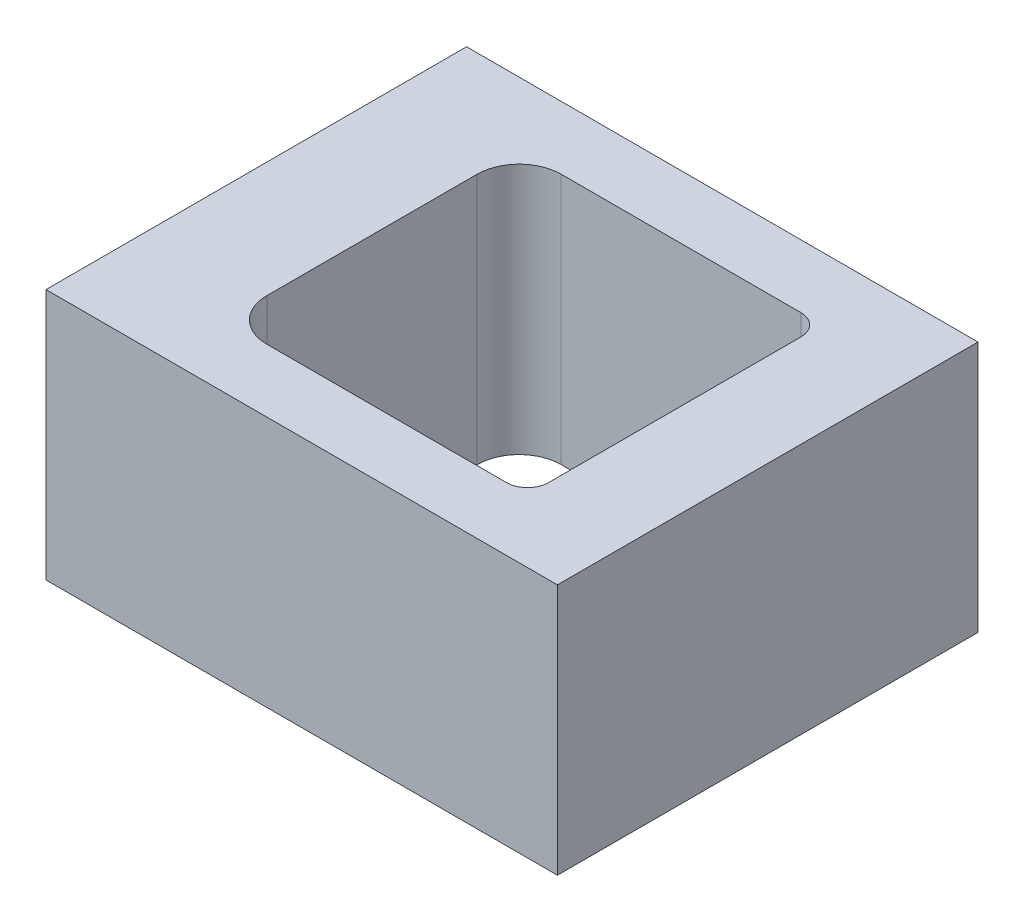
SolidWorks part; units mm, degrees
ref_plane "Front Plane" through (0, 0, 0) normal (0, 0, 1) x (1, 0, 0)
ref_plane "Top Plane" through (0, 0, 0) normal (0, 1, 0) x (1, 0, 0)
ref_plane "Right Plane" through (0, 0, 0) normal (1, 0, 0) x (0, 0, -1)
sketch "Sketch1" plane through (0, 0, 0) normal (0, 1, 0) x (1, 0, 0)
  line L1 (-77.216, -63.5) -> (77.216, -63.5)
  line L2 (-77.216, -63.5) -> (-77.216, 63.5)
  line L3 (-77.216, 63.5) -> (77.216, 63.5)
  line L4 (77.216, -63.5) -> (77.216, 63.5)
  line L5 (-77.216, -63.5) -> (77.216, 63.5) construction
  line L6 (-77.216, 63.5) -> (77.216, -63.5) construction
  line L14 (-42.291, 31.75) -> (-42.291, -31.75) construction
  line L15 (42.799, -44.45) -> (-29.591, -44.45) construction
  line L16 (49.149, 38.1) -> (49.149, -38.1) construction
  line L17 (42.799, 44.45) -> (-29.591, 44.45) construction
  line L18 (-42.291, 31.75) -> (-42.291, -31.75)
  line L19 (42.799, -44.45) -> (-29.591, -44.45)
  line L20 (49.149, 38.1) -> (49.149, -38.1)
  line L21 (42.799, 44.45) -> (-29.591, 44.45)
  arc A8 (-42.291, -31.75) -> (-29.591, -44.45) centre (-29.591, -31.75) ccw construction
  arc A9 (42.799, -44.45) -> (49.149, -38.1) centre (42.799, -38.1) ccw construction
  arc A10 (49.149, 38.1) -> (42.799, 44.45) centre (42.799, 38.1) ccw construction
  arc A11 (-29.591, 44.45) -> (-42.291, 31.75) centre (-29.591, 31.75) ccw construction
  arc A12 (-42.291, -31.75) -> (-29.591, -44.45) centre (-29.591, -31.75) ccw
  arc A13 (42.799, -44.45) -> (49.149, -38.1) centre (42.799, -38.1) ccw
  arc A14 (49.149, 38.1) -> (42.799, 44.45) centre (42.799, 38.1) ccw
  arc A15 (-29.591, 44.45) -> (-42.291, 31.75) centre (-29.591, 31.75) ccw
  point P0 (0, 0)
  dimension "D1" = 127
  dimension "D2" = 154.432
extrude "Boss-Extrude1" add sketch "Sketch1" along normal blind 75.946
